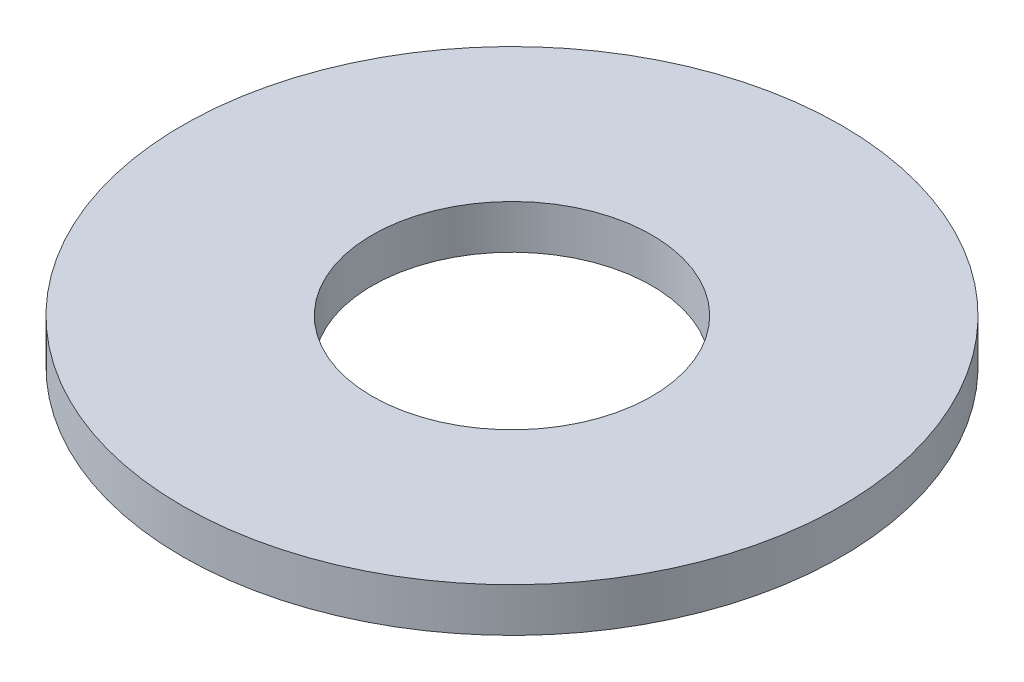
SolidWorks part; units mm, degrees
ref_plane "Front Plane" through (0, 0, 0) normal (0, 0, 1) x (1, 0, 0)
ref_plane "Top Plane" through (0, 0, 0) normal (0, 1, 0) x (1, 0, 0)
ref_plane "Right Plane" through (0, 0, 0) normal (1, 0, 0) x (0, 0, -1)
sketch "Sketch1" plane through (0, 0, 0) normal (0, 1, 0) x (1, 0, 0)
  circle A0 centre (0, 0) radius 82.5
  dimension "FLANGE_OD" = 165
extrude "Boss-Extrude1" add sketch "Sketch1" along normal blind 11
sketch "Sketch2" plane through (0, 0, 0) normal (0, 1, 0) x (1, 0, 0)
  circle A0 centre (0, 0) radius 35
  dimension "BORE_D" = 70
extrude "Cut-Extrude1" cut sketch "Sketch2" along normal through all
sketch "Sketch3" plane through (0, 11, 0) normal (0, 1, 0) x (1, 0, 0)
  circle A0 centre (0, 0) radius 24.8107 construction
  circle A1 centre (-24.8107, 0) radius 3.5274
  dimension "BOLT_D" = 7.0548
  dimension "BOLT_PCD" = 49.6214
extrude "Cut-Extrude2" cut sketch "Sketch3" against normal blind 6.6768 rebuild error yes
pattern_circular "CirPattern1" count 4 over 360 rebuild error yes
